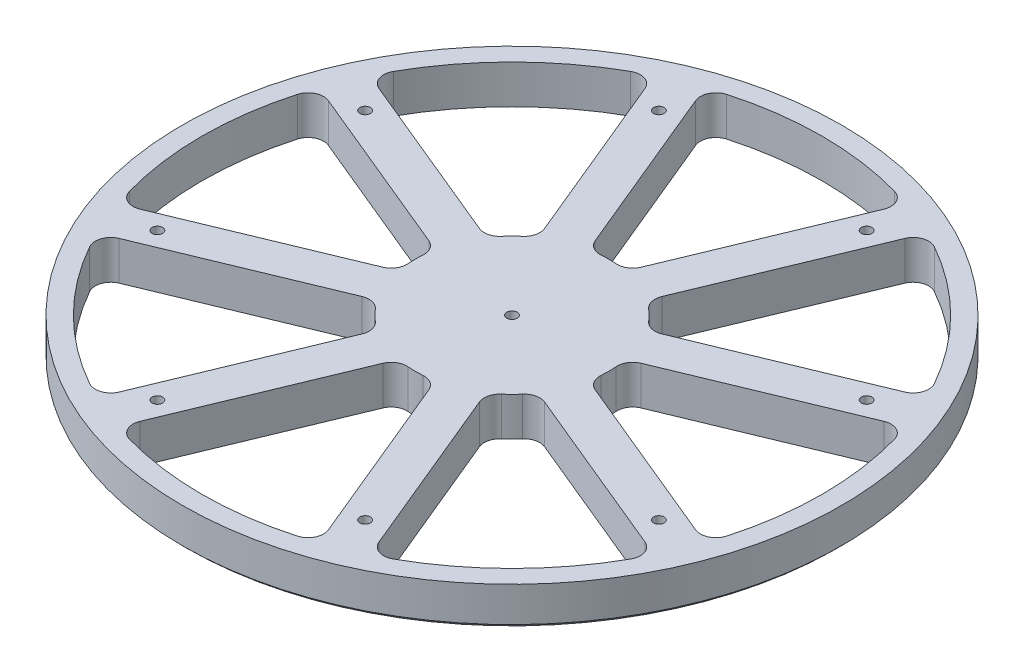
SolidWorks part; units mm, degrees
ref_plane "Front Plane" through (0, 0, 0) normal (0, 0, 1) x (1, 0, 0)
ref_plane "Top Plane" through (0, 0, 0) normal (0, 1, 0) x (1, 0, 0)
ref_plane "Right Plane" through (0, 0, 0) normal (1, 0, 0) x (0, 0, -1)
sketch "Sketch2" plane through (0, 0, 0) normal (1, 0, 0) x (0, 0, -1)
  line L0 (0, 0) -> (-84.9998, 0)
  line L1 (-84.9998, 0) -> (-84.9998, 10)
  line L2 (-84.9998, 10) -> (0, 10)
  line L5 (0, 10) -> (0, 0)
  dimension "D1" = 84.9998
  dimension "D2" = 10
ref_axis "Axis1" through (0, -0.75, 0) along (0, 1, 0)
revolve "Revolve1" add sketch "Sketch2" angle 360 about axis through (0, -0.75, 0) along (0, 1, 0)
hole_wizard "#6-32 Tapped Hole2" positions "Sketch6" profile "Sketch7" tap size "#6-32" standard "ANSI Inch" end condition through all
sketch "Sketch6" plane through (0, 10, 0) normal (0, 1, 0) x (1, 0, 0)
  line L0 (0, 0) -> (-53.438, 129.0108) construction
  line L2 (0, 0) -> (0, 109.0908) construction
  point P0 (-26.7878, 64.6716)
  dimension "D1" = 22.5
  dimension "D2" = 70
sketch "Sketch7" plane through (-26.7878, 10, -64.6716) normal (1, 0, 0) x (0, 0, 1)
  line L0 (0, 0) -> (0, 10)
  line L1 (0, 10) -> (1.3525, 10)
  line L2 (1.3525, 10) -> (1.3525, 0)
  line L5 (1.3525, 0) -> (0, 0)
  line L11 (0, -6.35) -> (0, 107.95) construction
  dimension "Thread Major Dia." = 2.7051
  dimension "Thru Tap Drill Depth" = 10
pattern_circular "CirPattern3" count 8 over 360 about axis through (0, -0.75, 0) along (0, 1, 0) of "#6-32 Tapped Hole2"
sketch "Sketch8" plane through (0, 10, 0) normal (0, 1, 0) x (1, 0, 0)
  line L4 (0, 0) -> (0, 93.9995) construction
  line L5 (0, 0) -> (113.8372, 0) construction
  line L6 (-4.7544, 24.5438) -> (-25.9354, 75.6791)
  line L7 (4.7544, 24.5438) -> (25.9354, 75.6791)
  line L8 (0, 0) -> (-26.7878, 64.6716) construction
  arc A0 (-4.7544, 24.5438) -> (4.7544, 24.5438) centre (0, 0) cw
  arc A1 (-25.9354, 75.6791) -> (25.9354, 75.6791) centre (0, 0) cw
  circle A2 centre (0, 0) radius 84.9998 construction
  dimension "D1" = 25
  dimension "D2" = 5
  dimension "D3" = 5
extrude "Cut-Extrude1" cut sketch "Sketch8" against normal through all
fillet "Fillet1" radius 4 4 edges at (4.7544, 5, -24.5438) (25.9354, 5, -75.6791) (-4.7544, 5, -24.5438) (-25.9354, 5, -75.6791)
pattern_circular "CirPattern4" count 8 over 360 about axis through (0, -0.75, 0) along (0, 1, 0) of "Cut-Extrude1", "Fillet1"
chamfer "Chamfer2" distance 1 angle 45 1 edges at (0, 0, -84.9998)
hole_wizard "#6-32 Tapped Hole1" positions "Sketch9" profile "Sketch11" tap size "#6-32" standard "ANSI Inch" end condition through all
sketch "Sketch9" plane through (0, 0, 0) normal (0, -1, 0) x (-1, 0, 0)
  point P0 (0, 0)
sketch "Sketch11" plane through (0, 0, 0) normal (1, 0, 0) x (0, 0, -1)
  line L0 (0, 0) -> (0, 10)
  line L1 (0, 10) -> (1.3525, 10)
  line L2 (1.3525, 10) -> (1.3525, 0)
  line L5 (1.3525, 0) -> (0, 0)
  line L11 (0, -6.35) -> (0, 107.95) construction
  dimension "Thru Tap Drill Dia." = 2.7051
  dimension "Thru Tap Drill Depth" = 10
cosmetic thread "Hole Thread1" parameters "D2"=3.5052
